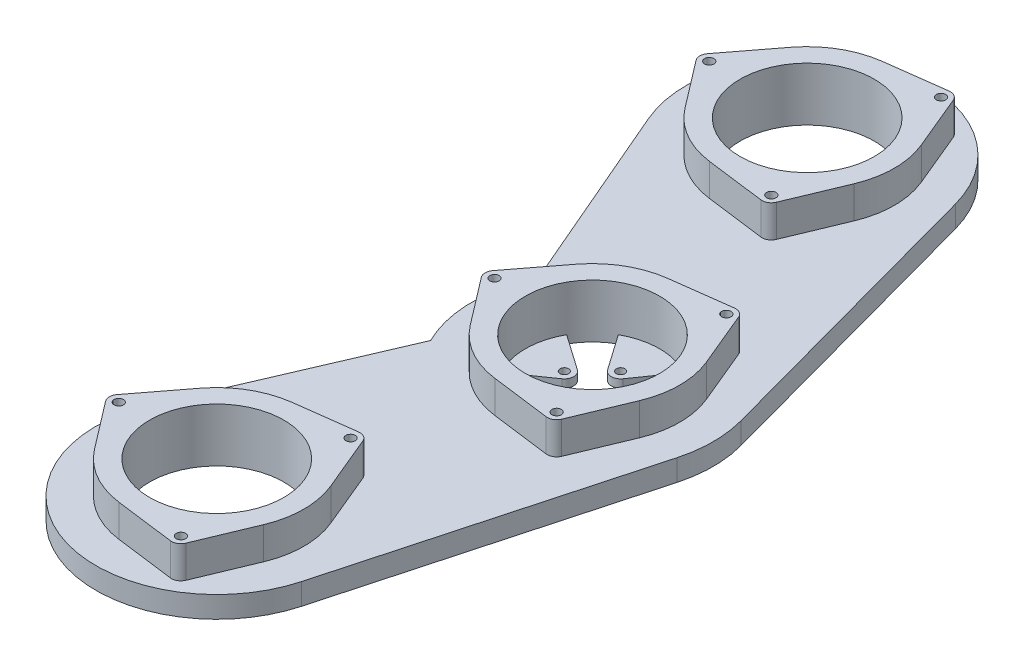
SolidWorks part; units mm, degrees
ref_plane "Alzado" through (0, 0, 0) normal (0, 0, 1) x (1, 0, 0)
ref_plane "Planta" through (0, 0, 0) normal (0, 1, 0) x (1, 0, 0)
ref_plane "Vista lateral" through (0, 0, 0) normal (1, 0, 0) x (0, 0, -1)
sketch "Croquis5" plane through (0, 0, 0) normal (0, 1, 0) x (1, 0, 0)
  line L0 (0, 176.3184) -> (0, -176.3184) construction
  line L1 (-217.2635, 0) -> (217.2635, 0) construction
  line L2 (13.4144, 121.8403) -> (43.4144, 11.8403)
  line L3 (43.4144, -11.8403) -> (13.4144, -121.8403)
  line L6 (-71.3458, 92.237) -> (-40.3113, 20)
  line L7 (-71.3458, -92.237) -> (-40.3113, -20)
  circle A0 centre (0, 0) radius 45
  circle A1 centre (-30, 110) radius 45
  circle A2 centre (-30, -110) radius 45
  point P6 (0, 0)
  point P9 (0, 0)
  dimension "D1" = 90
  dimension "D2" = 220
  dimension "D3" = 30
  dimension "D4" = 20
sketch "Croquis1" plane through (0, 0, 0) normal (0, 1, 0) x (1, 0, 0)
  line L16 (-71.3458, 92.237) -> (-40.3113, 20) construction
  line L17 (-71.3458, -92.237) -> (-40.3113, -20) construction
  line L18 (43.4144, -11.8403) -> (13.4144, -121.8403) construction
  line L19 (13.4144, 121.8403) -> (43.4144, 11.8403) construction
  line L20 (-71.3458, 92.237) -> (-40.3113, 20)
  line L21 (-71.3458, -92.237) -> (-40.3113, -20)
  line L22 (43.4144, -11.8403) -> (13.4144, -121.8403)
  line L23 (13.4144, 121.8403) -> (43.4144, 11.8403)
  circle A10 centre (-30, -110) radius 45 construction
  circle A11 centre (0, 0) radius 45 construction
  circle A12 centre (-30, 110) radius 45 construction
  arc A13 (-71.3458, -92.237) -> (13.4144, -121.8403) centre (-30, -110) ccw
  arc A14 (-40.3113, 20) -> (-40.3113, -20) centre (0, 0) ccw
  arc A15 (13.4144, 121.8403) -> (-71.3458, 92.237) centre (-30, 110) ccw
  arc A16 (43.4144, -11.8403) -> (43.4144, 11.8403) centre (0, 0) ccw
extrude "Saliente-Extruir1" add sketch "Croquis1" along normal blind 8
sketch "Croquis6" plane through (0, 8, 0) normal (0, 1, 0) x (1, 0, 0)
  line L2 (0, 0) -> (-32.5, 0) construction
  line L22 (-39.2808, 2.1253) -> (-25.8219, 19.7352)
  line L23 (-39.2808, -2.1253) -> (-25.8219, -19.7352)
  line L24 (21.481, 32.9555) -> (30.0022, 12.4948)
  line L25 (17.7998, 35.0809) -> (-4.1802, 32.23)
  line L26 (17.7998, -35.0809) -> (-4.1802, -32.23)
  line L27 (21.481, -32.9555) -> (30.0022, -12.4948)
  line L28 (0, 0) -> (-25.8219, 19.7352) construction
  line L33 (-69.2808, -107.8747) -> (-55.8219, -90.2648)
  line L36 (-8.519, -142.9555) -> (0.0022, -122.4948)
  line L40 (-69.2808, -112.1253) -> (-55.8219, -129.7352)
  line L42 (-30, -110) -> (-62.5, -110) construction
  line L45 (-30, -110) -> (-55.8219, -90.2648) construction
  line L46 (-12.2002, -74.9191) -> (-34.1802, -77.77)
  line L47 (-12.2002, -145.0809) -> (-34.1802, -142.23)
  line L48 (-8.519, -77.0445) -> (0.0022, -97.5052)
  line L49 (-69.2808, 107.8747) -> (-55.8219, 90.2648)
  line L50 (-12.2002, 145.0809) -> (-34.1802, 142.23)
  line L51 (-30, 110) -> (-55.8219, 129.7352) construction
  line L52 (-8.519, 142.9555) -> (0.0022, 122.4948)
  line L53 (-30, 110) -> (-62.5, 110) construction
  line L54 (-12.2002, 74.9191) -> (-34.1802, 77.77)
  line L55 (-69.2808, 112.1253) -> (-55.8219, 129.7352)
  line L56 (-8.519, 77.0445) -> (0.0022, 97.5052)
  arc A25 (-25.8219, -19.7352) -> (-4.1802, -32.23) centre (0, 0) ccw
  arc A26 (-39.2808, 2.1253) -> (-39.2808, -2.1253) centre (-36.5, 0) ccw
  arc A27 (21.481, 32.9555) -> (17.7998, 35.0809) centre (18.25, 31.6099) ccw
  arc A28 (17.7998, -35.0809) -> (21.481, -32.9555) centre (18.25, -31.6099) ccw
  arc A29 (-4.1802, 32.23) -> (-25.8219, 19.7352) centre (0, 0) ccw
  arc A30 (30.0022, -12.4948) -> (30.0022, 12.4948) centre (0, 0) ccw
  arc A43 (-55.8219, -129.7352) -> (-34.1802, -142.23) centre (-30, -110) ccw
  arc A44 (-8.519, -77.0445) -> (-12.2002, -74.9191) centre (-11.75, -78.3901) ccw
  arc A45 (-34.1802, -77.77) -> (-55.8219, -90.2648) centre (-30, -110) ccw
  arc A46 (-69.2808, -107.8747) -> (-69.2808, -112.1253) centre (-66.5, -110) ccw
  arc A47 (0.0022, -122.4948) -> (0.0022, -97.5052) centre (-30, -110) ccw
  arc A48 (-12.2002, -145.0809) -> (-8.519, -142.9555) centre (-11.75, -141.6099) ccw
  arc A49 (-34.1802, 142.23) -> (-55.8219, 129.7352) centre (-30, 110) ccw
  arc A50 (-12.2002, 74.9191) -> (-8.519, 77.0445) centre (-11.75, 78.3901) ccw
  arc A51 (-69.2808, 112.1253) -> (-69.2808, 107.8747) centre (-66.5, 110) ccw
  arc A52 (-55.8219, 90.2648) -> (-34.1802, 77.77) centre (-30, 110) ccw
  arc A53 (-8.519, 142.9555) -> (-12.2002, 145.0809) centre (-11.75, 141.6099) ccw
  arc A54 (0.0022, 97.5052) -> (0.0022, 122.4948) centre (-30, 110) ccw
  dimension "D1" = 32.5
  dimension "D2" = 7
  dimension "D3" = 4
  dimension "D5" = 32.5
  dimension "D6" = 7
  dimension "D4" = 3
  dimension "D9" = 32.5
  dimension "D10" = 7
  dimension "D7" = 32.5
  dimension "D8" = 4
  dimension "D11" = 32.5
  dimension "D12" = 4
  dimension "D13" = 32.5
extrude "Saliente-Extruir2" add sketch "Croquis6" along normal blind 12
sketch "Croquis7" plane through (0, 8, 0) normal (0, 1, 0) x (1, 0, 0)
  circle A26 centre (0, 0) radius 25
  circle A27 centre (-30, 110) radius 25
  circle A28 centre (-30, -110) radius 25
  circle A29 centre (-36.5, 0) radius 1.75
  circle A30 centre (18.25, -31.6099) radius 1.75
  circle A31 centre (18.25, 31.6099) radius 1.75
  circle A32 centre (-11.75, 141.6099) radius 1.75
  circle A33 centre (-66.5, 110) radius 1.75
  circle A34 centre (-11.75, 78.3901) radius 1.75
  circle A35 centre (-66.5, -110) radius 1.75
  circle A36 centre (-11.75, -141.6099) radius 1.75
  circle A37 centre (-11.75, -78.3901) radius 1.75
  dimension "D1" = 50
  dimension "D2" = 3.5
extrude "Cortar-Extruir3" cut sketch "Croquis7" against normal through all both and the other way through all
sketch "Croquis8" plane through (0, 0, 0) normal (0, -1, 0) x (1, 0, 0)
  line L0 (0, 0) -> (0, 10.5) construction
  line L1 (0, 10.5) -> (0, 0) construction
  circle A0 centre (0, 0) radius 10.5 construction
  circle A1 centre (0, 10.5) radius 1.6
  circle A2 centre (10.5, 0) radius 1.6
  circle A3 centre (0, -10.5) radius 1.6
  circle A4 centre (-10.5, 0) radius 1.6
  point P5 (0, 0)
  point P7 (0, 0)
  point P14 (0, 0)
  dimension "D1" = 3.2
  dimension "D3" = 0
  dimension "D4" = 21
  dimension "D2" = 4
sketch "Croquis9" plane through (0, 0, 0) normal (0, -1, 0) x (1, 0, 0)
  line L0 (-2.867, 8.4925) -> (-12.1999, 21.8212)
  line L1 (2.867, 8.4925) -> (12.1999, 21.8212)
  line L2 (0, 10.5) -> (0, 19.0199) construction
  line L3 (8.4925, 2.867) -> (21.8212, 12.1999)
  line L4 (8.4925, -2.867) -> (21.8212, -12.1999)
  line L5 (2.867, -8.4925) -> (12.1999, -21.8212)
  line L6 (-2.867, -8.4925) -> (-12.1999, -21.8212)
  line L7 (-8.4925, -2.867) -> (-21.8212, -12.1999)
  line L8 (-8.4925, 2.867) -> (-21.8212, 12.1999)
  arc A0 (-2.867, 8.4925) -> (2.867, 8.4925) centre (0, 10.5) ccw
  circle A1 centre (0, 0) radius 25 construction
  arc A2 (-21.8212, 12.1999) -> (-21.8212, -12.1999) centre (0, 0) ccw
  arc A3 (8.4925, 2.867) -> (8.4925, -2.867) centre (10.5, 0) ccw
  arc A4 (2.867, -8.4925) -> (-2.867, -8.4925) centre (0, -10.5) ccw
  arc A5 (-8.4925, -2.867) -> (-8.4925, 2.867) centre (-10.5, 0) ccw
  arc A6 (12.1999, 21.8212) -> (-12.1999, 21.8212) centre (0, 0) ccw
  arc A7 (21.8212, -12.1999) -> (21.8212, 12.1999) centre (0, 0) ccw
  arc A8 (-12.1999, -21.8212) -> (12.1999, -21.8212) centre (0, 0) ccw
  point P29 (0, 0)
  dimension "D1" = 7
  dimension "D2" = 70
  dimension "D3" = 4
extrude "Saliente-Extruir4" add sketch "Croquis9" against normal blind 3
sketch "Croquis10" plane through (0, 8, 0) normal (0, 1, 0) x (1, 0, 0)
  circle A0 centre (-10.5, 0) radius 1.6 construction
  circle A1 centre (0, -10.5) radius 1.6 construction
  circle A2 centre (10.5, 0) radius 1.6 construction
  circle A3 centre (0, 10.5) radius 1.6 construction
  circle A4 centre (-10.5, 0) radius 1.6
  circle A5 centre (0, -10.5) radius 1.6
  circle A6 centre (10.5, 0) radius 1.6
  circle A7 centre (0, 10.5) radius 1.6
extrude "Cortar-Extruir4" cut sketch "Croquis10" against normal through all
